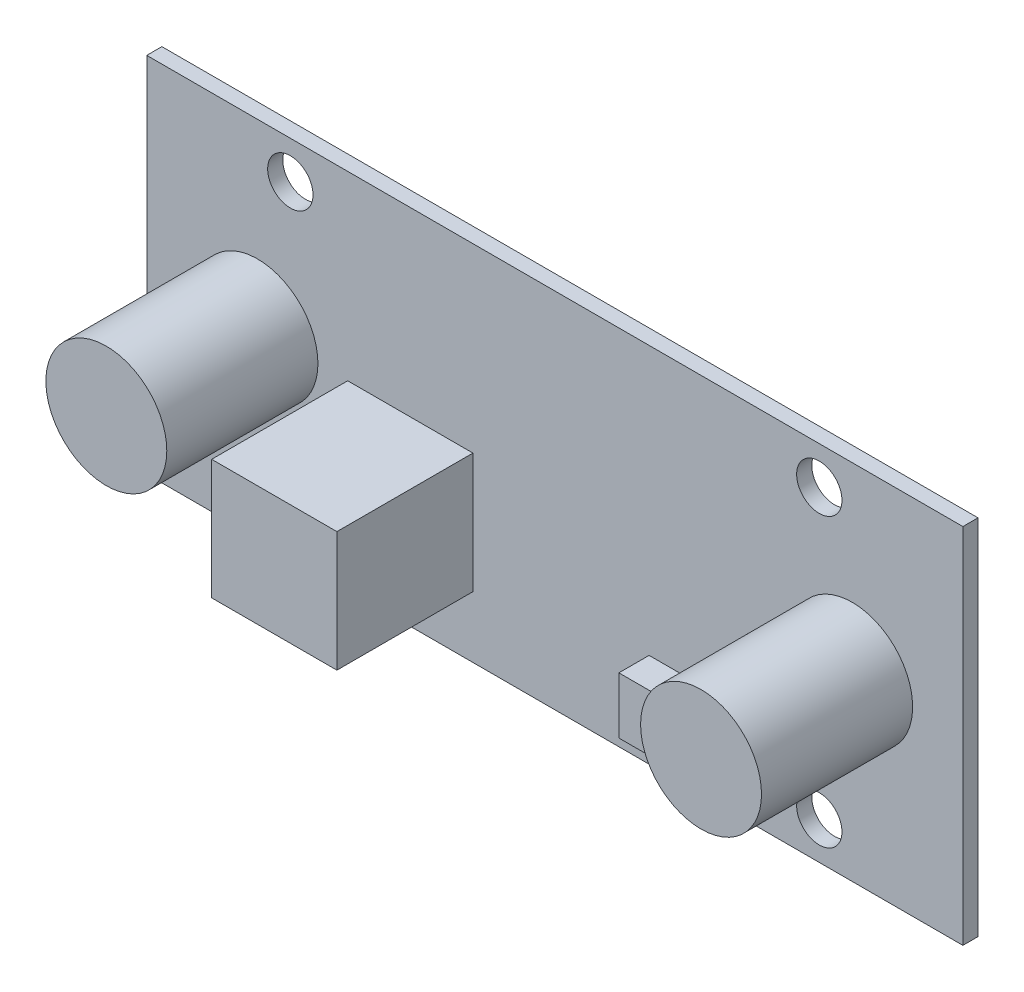
SolidWorks part; units mm, degrees
ref_plane "Front Plane" through (0, 0, 0) normal (0, 0, 1) x (1, 0, 0)
ref_plane "Top Plane" through (0, 0, 0) normal (0, 1, 0) x (1, 0, 0)
ref_plane "Right Plane" through (0, 0, 0) normal (1, 0, 0) x (0, 0, -1)
sketch "Sketch1" plane through (0, 0, 0) normal (0, 0, 1) x (1, 0, 0)
  line L1 (0, 0) -> (54, 0)
  line L2 (0, 0) -> (0, 24)
  line L3 (0, 24) -> (54, 24)
  line L4 (54, 0) -> (54, 24)
  line L6 (33.2379, 6.2362) -> (39.9092, 6.2362)
  line L7 (13.2941, 12) -> (21.5806, 12)
  line L8 (13.2941, 12) -> (13.2941, 4.0592)
  line L9 (13.2941, 4.0592) -> (21.5806, 4.0592)
  line L10 (21.5806, 12) -> (21.5806, 4.0592)
  line L11 (33.2379, 6.2362) -> (33.2379, 2.5)
  line L12 (33.2379, 2.5) -> (39.9092, 2.5)
  line L13 (39.9092, 6.2362) -> (39.9092, 2.5)
  circle A0 centre (9.5, 21.5) radius 1.5
  circle A1 centre (9.5, 2.5) radius 1.5
  circle A2 centre (44.5, 2.5) radius 1.5
  circle A3 centre (44.5, 21.5) radius 1.5
  circle A4 centre (7.325, 12) radius 4
  circle A5 centre (46.675, 12) radius 4
  dimension "D3" = 3
  dimension "D4" = 3
  dimension "D5" = 19
  dimension "D6" = 2.5
  dimension "D7" = 9.5
  dimension "D8" = 35
  dimension "D9" = 35
  dimension "D10" = 9.5
  dimension "D1" = 54
  dimension "D2" = 24
extrude "Boss-Extrude1" add sketch "Sketch1" along normal blind 1
extrude "Boss-Extrude2" add sketch "Sketch1<2>" along normal blind 11 contours A4 | A5 region at (7.325, 12, 0) region at (46.675, 12, 0)
sketch "Sketch1<2>" plane through (0, 0, 0) normal (0, 0, 1) x (1, 0, 0) same geometry as "Sketch1"
extrude "Boss-Extrude3" add sketch "Sketch1<3>" along normal blind 10 contours L10 L7 L8 L9 region at (17.4373, 8.0296, 0)
sketch "Sketch1<3>" plane through (0, 0, 0) normal (0, 0, 1) x (1, 0, 0) same geometry as "Sketch1"
extrude "Boss-Extrude4" add sketch "Sketch1<4>" along normal blind 3 contours L13 L6 L11 L12 region at (36.5735, 4.3681, 0)
sketch "Sketch1<4>" plane through (0, 0, 0) normal (0, 0, 1) x (1, 0, 0) same geometry as "Sketch1"
